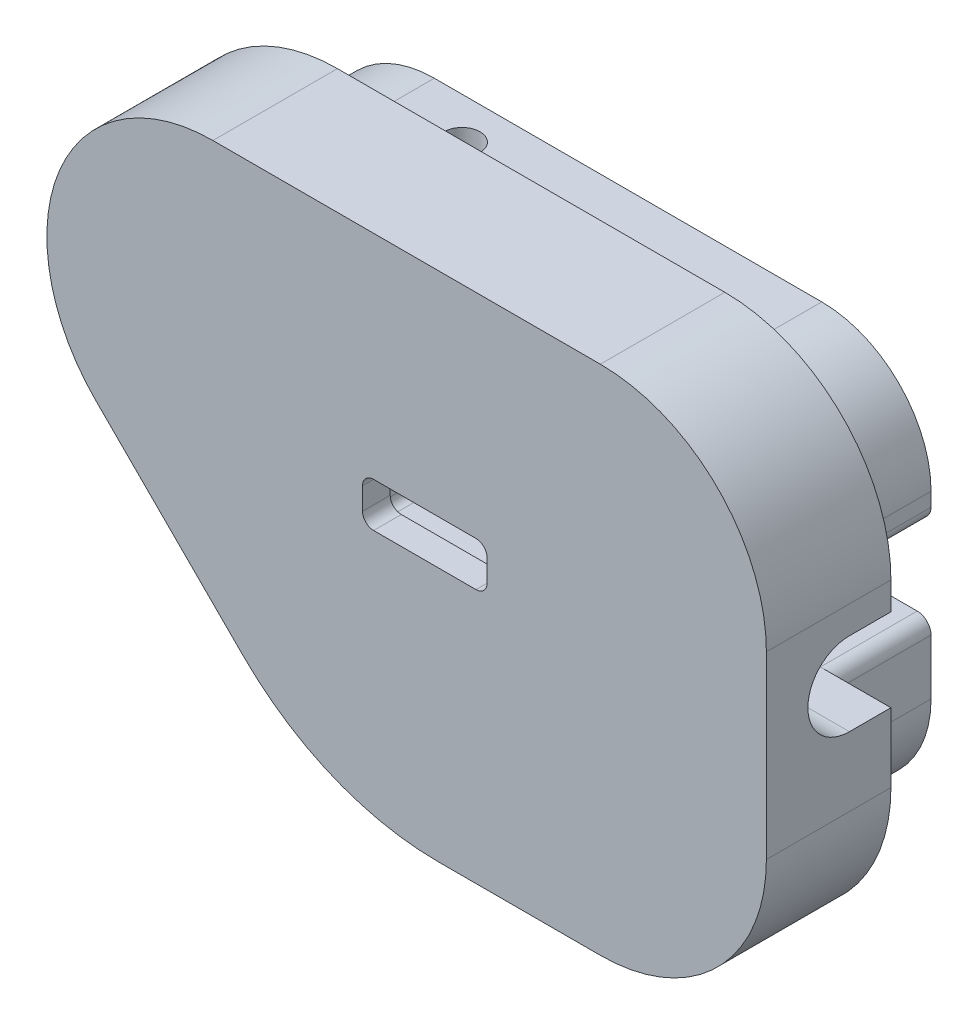
SolidWorks part; units mm, degrees
ref_plane "前视基准面" through (0, 0, 0) normal (0, 0, 1) x (1, 0, 0)
ref_plane "上视基准面" through (0, 0, 0) normal (0, 1, 0) x (1, 0, 0)
ref_plane "右视基准面" through (0, 0, 0) normal (1, 0, 0) x (0, 0, -1)
other "Configuration Table"
sketch "草图2" plane through (0, 0, 0) normal (0, 0, 1) x (1, 0, 0)
  line L0 (-24.799, -3.4853) -> (-14.1421, -14.1421)
  line L1 (0, -20) -> (11.6863, -20)
  line L2 (23.6863, -8) -> (23.6863, 5)
  line L3 (11.6863, 17) -> (-16.3137, 17)
  arc A0 (-16.3137, 17) -> (-24.799, -3.4853) centre (-16.3137, 5) ccw
  arc A1 (-14.1421, -14.1421) -> (0, -20) centre (0, 0) ccw
  arc A2 (11.6863, -20) -> (23.6863, -8) centre (11.6863, -8) ccw
  arc A3 (23.6863, 5) -> (11.6863, 17) centre (11.6863, 5) ccw
extrude "凸台-拉伸1" add sketch "草图2" against normal blind 9
sketch "草图3" plane through (0, 0, -9) normal (0, 0, -1) x (-1, 0, 0)
  line L0 (16.3137, 12.9) -> (-11.6863, 12.9)
  line L1 (-19.5863, 5) -> (-19.5863, -8)
  line L2 (-11.6863, -15.9) -> (0, -15.9)
  line L3 (11.243, -11.243) -> (21.8999, -0.5861)
  line L4 (16.3137, 17) -> (-11.6863, 17)
  line L5 (-23.6863, 5) -> (-23.6863, -8)
  line L6 (-11.6863, -20) -> (0, -20)
  line L7 (14.1421, -14.1421) -> (24.799, -3.4853)
  line L8 (16.3137, 17) -> (-11.6863, 17) construction
  line L9 (-23.6863, 5) -> (-23.6863, -8) construction
  line L10 (-11.6863, -20) -> (0, -20) construction
  line L11 (14.1421, -14.1421) -> (24.799, -3.4853) construction
  arc A0 (21.8999, -0.5861) -> (16.3137, 12.9) centre (16.3137, 5) ccw
  arc A1 (-11.6863, 12.9) -> (-19.5863, 5) centre (-11.6863, 5) ccw
  arc A2 (-19.5863, -8) -> (-11.6863, -15.9) centre (-11.6863, -8) ccw
  arc A3 (0, -15.9) -> (11.243, -11.243) centre (0, 0) ccw
  arc A4 (24.799, -3.4853) -> (16.3137, 17) centre (16.3137, 5) ccw
  arc A5 (-11.6863, 17) -> (-23.6863, 5) centre (-11.6863, 5) ccw
  arc A6 (-23.6863, -8) -> (-11.6863, -20) centre (-11.6863, -8) ccw
  arc A7 (0, -20) -> (14.1421, -14.1421) centre (0, 0) ccw
  arc A8 (24.799, -3.4853) -> (16.3137, 17) centre (16.3137, 5) ccw construction
  arc A9 (-11.6863, 17) -> (-23.6863, 5) centre (-11.6863, 5) ccw construction
  arc A10 (-23.6863, -8) -> (-11.6863, -20) centre (-11.6863, -8) ccw construction
  arc A11 (0, -20) -> (14.1421, -14.1421) centre (0, 0) ccw construction
  dimension "D1" = 0
  dimension "D2" = 4.1
extrude "凸台-拉伸2" add sketch "草图3" along normal blind 7
sketch "草图6" plane through (0, 12.9, 0) normal (0, 1, 0) x (1, 0, 0)
  line L2 (-28.3137, 0) -> (-28.3137, 9) construction
  line L3 (-16.3137, 9) -> (11.6863, 9) construction
  circle A0 centre (-11.3137, 13) radius 1.3
  dimension "D1" = 2.6
  dimension "D2" = 17
  dimension "D3" = 4
extrude "切除-拉伸1" cut sketch "草图6" against normal blind 6
sketch "草图7" plane through (0, -15.9, 0) normal (0, -1, 0) x (1, 0, 0)
  line L0 (-28.3137, 0) -> (-28.3137, -9) construction
  line L3 (0, -9) -> (11.6863, -9) construction
  circle A0 centre (6.6863, -13) radius 1.3
  dimension "D1" = 35
  dimension "D3" = 2.6
  dimension "D2" = 4
extrude "切除-拉伸2" cut sketch "草图7" against normal blind 6
sketch "草图8" plane through (0, 0, -16) normal (0, 0, -1) x (-1, 0, 0)
  line L5 (-4, 4) -> (14, 4)
  line L6 (-5, 3) -> (-5, -3)
  line L7 (-4, -4) -> (14, -4)
  line L8 (15, 3) -> (15, -3)
  line L9 (-5, 4) -> (15, -4) construction
  line L10 (-5, -4) -> (15, 4) construction
  arc A0 (14, 4) -> (15, 3) centre (14, 3) cw
  arc A1 (15, -3) -> (14, -4) centre (14, -3) cw
  arc A2 (-4, -4) -> (-5, -3) centre (-4, -3) cw
  arc A3 (-5, 3) -> (-4, 4) centre (-4, 3) cw
  point P0 (5, 0)
  dimension "D1" = 1
extrude "切除-拉伸3" cut sketch "草图8" against normal offset from surface (14 mm away) 2 up to face at (1.6293, -3.1499, 0)
sketch "草图9" plane through (0, 0, -2) normal (0, 0, -1) x (-1, 0, 0)
  line L0 (-5, 3) -> (-5, -3) construction
  line L1 (-2.7, 1.6) -> (4.7, 1.6)
  line L2 (-3.5, 0.8) -> (-3.5, -0.8)
  line L3 (-2.7, -1.6) -> (4.7, -1.6)
  line L4 (5.5, 0.8) -> (5.5, -0.8)
  line L5 (-3.5, 1.6) -> (5.5, -1.6) construction
  line L6 (-3.5, -1.6) -> (5.5, 1.6) construction
  arc A0 (4.7, -1.6) -> (5.5, -0.8) centre (4.7, -0.8) ccw
  arc A1 (5.5, 0.8) -> (4.7, 1.6) centre (4.7, 0.8) ccw
  arc A2 (-2.7, -1.6) -> (-3.5, -0.8) centre (-2.7, -0.8) cw
  arc A3 (-3.5, 0.8) -> (-2.7, 1.6) centre (-2.7, 0.8) cw
  point P0 (1, 0)
  dimension "D4" = 0.8
  dimension "D1" = 9
  dimension "D2" = 3.2
  dimension "D3" = 6
extrude "切除-拉伸4" cut sketch "草图9" against normal up to surface (2 mm away) up to face at (1.6293, -3.1499, 0)
sketch "草图10" plane through (0, 0, -2) normal (0, 0, -1) x (-1, 0, 0)
  line L0 (-5, 3) -> (-5, -3) construction
  line L1 (-4, -2.6) -> (6, -2.6)
  line L2 (-4.6, -2) -> (-4.6, 2)
  line L3 (-4, 2.6) -> (6, 2.6)
  line L4 (6.6, -2) -> (6.6, 2)
  line L5 (-4.6, -2.6) -> (6.6, 2.6) construction
  line L6 (-4.6, 2.6) -> (6.6, -2.6) construction
  line L11 (14, 4) -> (-4, 4)
  line L12 (-5, 3) -> (-5, -3)
  line L13 (-4, -4) -> (14, -4)
  line L14 (15, -3) -> (15, 3)
  line L15 (14, 4) -> (-4, 4)
  line L16 (-5, 3) -> (-5, -3)
  line L17 (-4, -4) -> (14, -4)
  line L18 (15, -3) -> (15, 3)
  arc A0 (6, -2.6) -> (6.6, -2) centre (6, -2) ccw
  arc A1 (6.6, 2) -> (6, 2.6) centre (6, 2) ccw
  arc A2 (-4, -2.6) -> (-4.6, -2) centre (-4, -2) cw
  arc A3 (-4.6, 2) -> (-4, 2.6) centre (-4, 2) cw
  arc A8 (15, 3) -> (14, 4) centre (14, 3) ccw
  arc A9 (-4, 4) -> (-5, 3) centre (-4, 3) ccw
  arc A10 (-5, -3) -> (-4, -4) centre (-4, -3) ccw
  arc A11 (14, -4) -> (15, -3) centre (14, -3) ccw
  arc A12 (15, 3) -> (14, 4) centre (14, 3) ccw
  arc A13 (-4, 4) -> (-5, 3) centre (-4, 3) ccw
  arc A14 (-5, -3) -> (-4, -4) centre (-4, -3) ccw
  arc A15 (14, -4) -> (15, -3) centre (14, -3) ccw
  point P0 (1, 0)
  dimension "D4" = 0.6
  dimension "D1" = 6
  dimension "D2" = 11.2
  dimension "D3" = 5.2
  dimension "D5" = 0
extrude "凸台-拉伸4" add sketch "草图10" along normal blind 9.4
sketch "草图11" plane through (0, 0, -11.4) normal (0, 0, -1) x (-1, 0, 0)
  circle A0 centre (10, 0) radius 1.3
extrude "切除-拉伸5" cut sketch "草图11" against normal blind 6
chamfer "倒角1" distance 0.4 angle 70 1 edges at (-11.3, 0, -11.4) first distance on face at (-11.3, 0, -11.4)
sketch "草图14" plane through (0, 0, -16) normal (0, 0, -1) x (-1, 0, 0)
  line L4 (-10.5, 3) -> (-23.6863, 3)
  line L5 (-23.6863, -8) -> (-23.6863, 5) construction
  line L6 (-23.6863, 3) -> (-23.6863, -3)
  line L7 (-23.6863, -3) -> (-10.5, -3)
  arc A1 (-10.5, -3) -> (-10.5, 3) centre (-10.5, 0) ccw
  point P1 (0, 0)
  point P6 (0, 0)
extrude "切除-拉伸6" cut sketch "草图14" against normal offset from surface (13 mm away) 3 up to face at (-1, 0, 0)
fillet "圆角1" radius 3 3 edges at (17.0931, -3, -3) (17.0931, 3, -3) (7.5, 0, -3)
fillet "圆角2" radius 1 2 edges at (19.5863, -3, -12.5) (19.5863, 3, -12.5)
